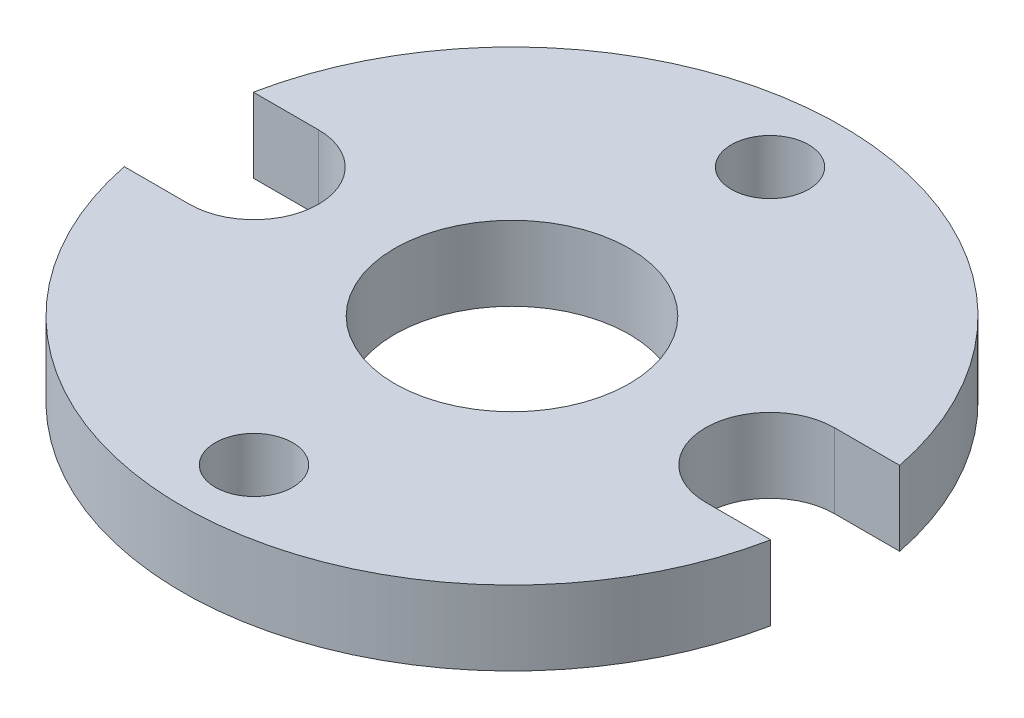
SolidWorks part; units mm, degrees
ref_plane "Front Plane" through (0, 0, 0) normal (0, 0, 1) x (1, 0, 0)
ref_plane "Top Plane" through (0, 0, 0) normal (0, 1, 0) x (1, 0, 0)
ref_plane "Right Plane" through (0, 0, 0) normal (1, 0, 0) x (0, 0, -1)
sketch "Sketch1" plane through (0, 0, 0) normal (0, 1, 0) x (1, 0, 0)
  line L0 (11, 0) -> (-11, 0) construction
  line L1 (-11, 2.75) -> (-13.7782, 2.75)
  line L2 (-11, -2.75) -> (-13.7782, -2.75)
  line L3 (13.7782, 2.75) -> (11, 2.75)
  line L4 (11, -2.75) -> (13.7782, -2.75)
  arc A0 (13.7782, 2.75) -> (-13.7782, 2.75) centre (0, 0) ccw
  circle A1 centre (0, 0) radius 5
  arc A2 (11, 2.75) -> (11, -2.75) centre (11, 0) ccw
  arc A3 (-11, -2.75) -> (-11, 2.75) centre (-11, 0) ccw
  arc A4 (-13.7782, -2.75) -> (13.7782, -2.75) centre (0, 0) ccw
  circle A5 centre (0, 11) radius 1.65
  circle A6 centre (0, -11) radius 1.65
  circle A7 centre (0, 0) radius 11 construction
  point P11 (0, 0)
  point P19 (0, -11)
  point P20 (0, 11)
  dimension "D1" = 28.1
  dimension "D2" = 10
  dimension "D4" = 5.5
  dimension "D5" = 3.3
  dimension "D3" = 22
extrude "Boss-Extrude1" add sketch "Sketch1" along normal blind 3.175
